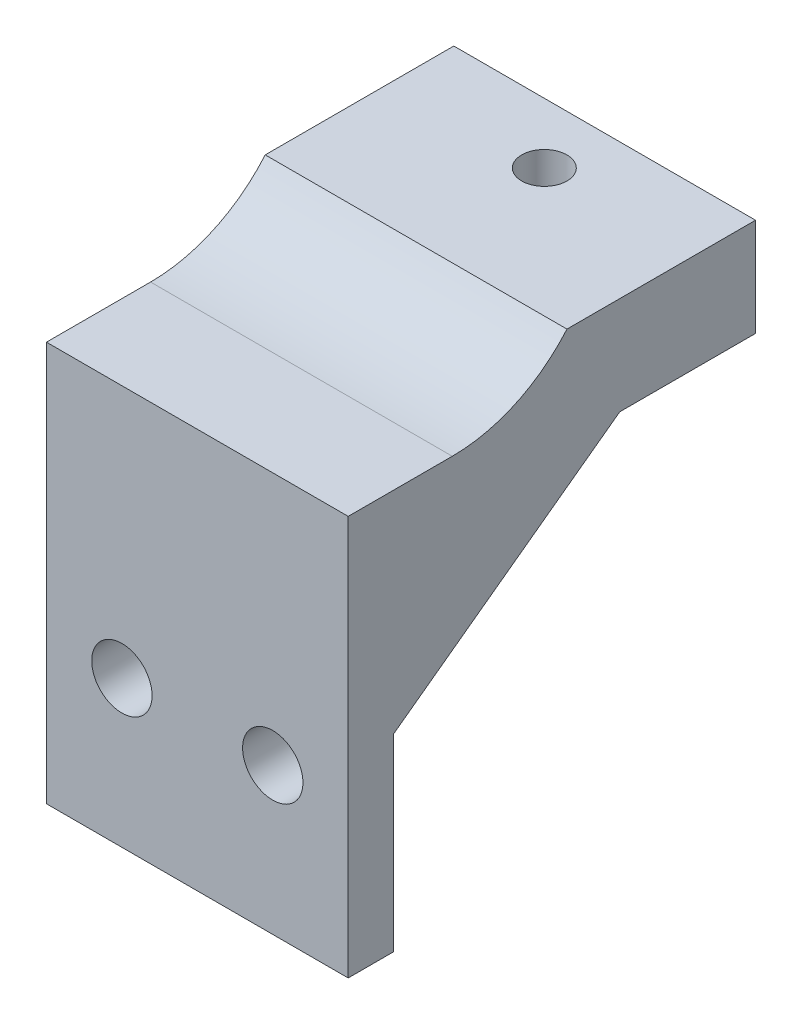
SolidWorks part; units mm, degrees
ref_plane "前视基准面" through (0, 0, 0) normal (0, 0, 1) x (1, 0, 0)
ref_plane "上视基准面" through (0, 0, 0) normal (0, 1, 0) x (1, 0, 0)
ref_plane "右视基准面" through (0, 0, 0) normal (1, 0, 0) x (0, 0, -1)
sketch "草图1" plane through (0, 0, 0) normal (0, 0, 1) x (1, 0, 0)
  line L0 (0, -55) -> (0, -25)
  line L1 (0, -25) -> (20, -25)
  line L2 (20, -25) -> (20, -55)
  line L4 (20, -28.5) -> (0, -28.5)
  line L13 (0, -55) -> (20, -55)
  circle A10 centre (5, -45.2915) radius 2
  circle A12 centre (15, -45.2915) radius 2
extrude "凸台-拉伸1" add sketch "草图1" along normal blind 3 contours L0 L13 L2 L4 A12 A10 region at (10, -41.5737, 0)
sketch "草图2" plane through (0, 0, 0) normal (0, 0, 1) x (1, 0, 0)
  line L0 (0, -28.5) -> (20, -28.5)
  line L1 (20, -28.5) -> (20, -31.5)
  line L2 (20, -31.5) -> (0, -31.5)
  line L3 (0, -31.5) -> (0, -28.5)
extrude "凸台-拉伸2" add sketch "草图2" against normal blind 24
sketch "草图3" plane through (0, 0, 0) normal (1, 0, 0) x (0, 0, -1)
  line L0 (0, -31.5) -> (0, -42.5)
  line L1 (0, -42.5) -> (15, -31.5)
  line L2 (15, -31.5) -> (0, -31.5)
extrude "凸台-拉伸3" add sketch "草图3" along normal blind 2
ref_plane "基准面1" through (10, 0, 0) normal (1, 0, 0) x (0, 0, -1)
mirror "镜向1" about plane through (10, 0, 0) normal (1, 0, 0) of "凸台-拉伸3"
sketch "草图4" plane through (0, -28.5, 0) normal (0, 1, 0) x (1, 0, 0)
  circle A0 centre (10, 20) radius 1.5
sketch "草图5" plane through (0, 0, 0) normal (1, 0, 0) x (0, 0, -1)
  line L0 (24, -28.5) -> (11.5, -28.5)
  line L1 (11.5, -28.5) -> (11.5, -25)
  line L2 (11.5, -25) -> (24, -25)
  line L3 (24, -25) -> (24, -28.5)
extrude "凸台-拉伸4" add sketch "草图5" along normal blind 20
extrude "切除-拉伸1" cut sketch "草图4" against normal mid plane 20
fillet "圆角1" radius 10 1 edges at (10, -28.5, -11.5)
